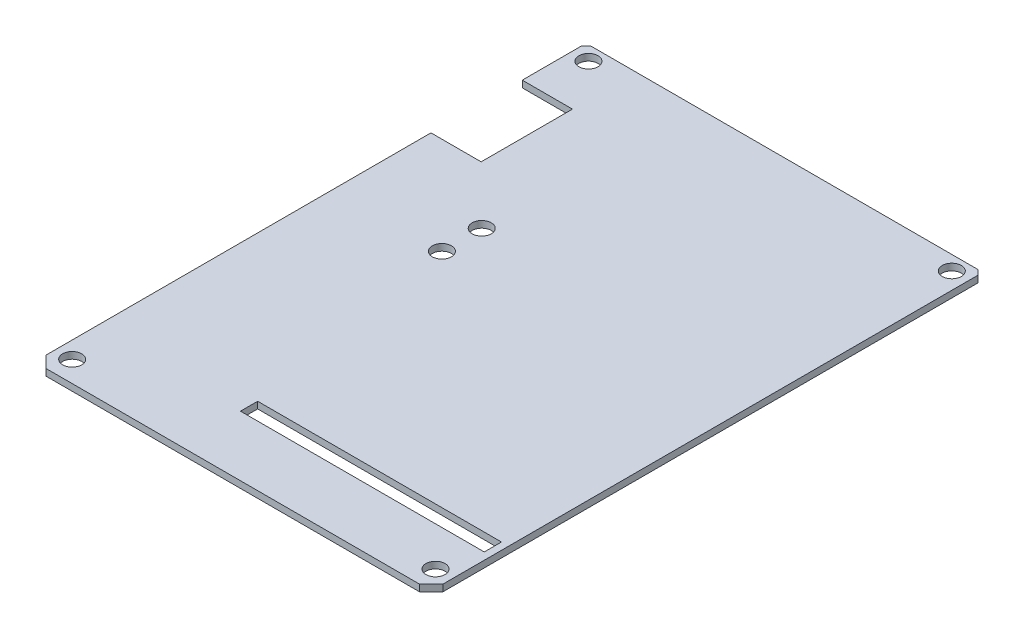
SolidWorks part; units mm, degrees
ref_plane "Front Plane" through (0, 0, 0) normal (0, 0, 1) x (1, 0, 0)
ref_plane "Top Plane" through (0, 0, 0) normal (0, 1, 0) x (1, 0, 0)
ref_plane "Right Plane" through (0, 0, 0) normal (1, 0, 0) x (0, 0, -1)
sketch "Sketch1" plane through (0, 0, 0) normal (0, 1, 0) x (1, 0, 0)
  line L17 (21.25, -27.4901) -> (19.2401, -29.5)
  line L33 (-21.25, 29.5) -> (21.25, 29.5)
  line L34 (-21.25, 29.5) -> (-21.25, -29.5)
  line L35 (-21.25, -29.5) -> (21.25, -29.5)
  line L36 (21.25, 29.5) -> (21.25, -29.5)
  line L37 (-21.25, 29.5) -> (21.25, -29.5) construction
  line L38 (-21.25, -29.5) -> (21.25, 29.5) construction
  line L39 (0, -29.5) -> (0, 29.5) construction
  line L40 (-21.25, -27.4901) -> (-19.2401, -29.5)
  line L41 (21.25, 0) -> (-21.25, 0) construction
  line L42 (21.25, 27.4901) -> (19.2401, 29.5)
  line L43 (-21.25, 27.4901) -> (-19.2401, 29.5)
  line L44 (-20.2401, 28.5) -> (20.2401, 28.5)
  line L45 (-20.2401, -28.5) -> (20.2401, -28.5)
  line L46 (-20.75, -27.9901) -> (-20.75, 27.9901)
  line L47 (20.75, 27.9901) -> (20.75, -27.9901)
  line L56 (-19, -27) -> (19, -27) construction
  circle A13 centre (-9.45, 6.2845) radius 1
  circle A18 centre (-19, -27) radius 1
  circle A19 centre (19, -27) radius 1
  circle A22 centre (-19, 27) radius 1
  circle A23 centre (19, 27) radius 1
  circle A24 centre (-9.45, 2.1155) radius 1
  point P4 (0, 0)
  point P12 (0, 0)
  point P14 (0, 0)
  point P21 (0, -27)
  point P22 (0, 0)
  point P24 (-12.6269, 17.0486)
  dimension "D1" = 42.5
  dimension "D6" = 2.0099
  dimension "D9" = 2
  dimension "D3" = 19
  dimension "D5" = 2.0099
  dimension "D2" = 59
  dimension "D12" = 1
  dimension "D4" = 2
  dimension "D8" = 27
  dimension "D13" = 0.5
  dimension "D14" = 0.5
extrude "Boss-Extrude1" add sketch "Sketch1" along normal blind 0.7 contours L34 L35 L17 L36 L33 A19 A13 region at (0.0253, 0, 0.0112)
sketch "Sketch2" plane through (0, 0.7, 0) normal (0, 1, 0) x (1, 0, 0)
  line L1 (-20, -22.9) -> (20, -22.9)
  line L2 (-20, -22.9) -> (-20, -21.1)
  line L3 (-20, -21.1) -> (20, -21.1)
  line L4 (20, -22.9) -> (20, -21.1)
  line L5 (-20, -22.9) -> (20, -21.1) construction
  line L6 (-20, -21.1) -> (20, -22.9) construction
  line L7 (0, 0) -> (0, -22.9) construction
  line L10 (-5.5029, -21.1) -> (-5.5029, -22.9)
  line L11 (-5.25, -22.6) -> (-5.25, -21.1) construction
  point P4 (0, -22)
  dimension "D1" = 22
  dimension "D2" = 20
  dimension "D3" = 1.8
  dimension "D4" = 0.2529
extrude "Cut-Extrude1" cut sketch "Sketch2" against normal blind 10 contours L3 L10 L1 L4 region at (7.2486, 0.7, 22)
sketch "Sketch5" plane through (0, 0.7, 0) normal (0, 1, 0) x (1, 0, 0)
  line L0 (-20.2401, -28.5) -> (20.2401, -28.5) construction
  line L1 (-19.5401, -28.5) -> (19.5401, -28.5) construction
  line L2 (-19.5401, -28.5) -> (-19.5401, -29.2) construction
  line L3 (-19.5401, -29.2) -> (19.5401, -29.2)
  line L4 (19.5401, -28.5) -> (19.5401, -29.2) construction
  line L5 (-19.5401, -28.5) -> (19.5401, -29.2) construction
  line L6 (-19.5401, -29.2) -> (19.5401, -28.5) construction
  line L7 (0, -28.5) -> (0, -32.1934) construction
  line L9 (-19.5401, -29.2) -> (-20.2401, -28.5)
  line L10 (19.5401, -29.2) -> (20.2401, -28.5)
  line L11 (-20.2401, -28.5) -> (20.2401, -28.5)
  line L12 (-20.75, -27.9901) -> (-20.2401, -28.5) construction
  point P4 (0, -28.85)
  point P11 (18.5758, -28.5)
  point P16 (-20.5591, -28.5)
  point P19 (0, 0)
  dimension "D1" = 0.7
extrude "Boss-Extrude2" add sketch "Sketch5" against normal up to surface (0.7 mm away) up to face at (19, 0, -26)
sketch "Sketch6" plane through (0, 0.7, 0) normal (0, 1, 0) x (1, 0, 0)
  line L0 (-20.75, -27.9901) -> (-20.75, 27.9901) construction
  line L1 (-20.75, 21.8236) -> (-15.5, 21.8236)
  line L2 (-20.75, 21.8236) -> (-20.75, 12.2736)
  line L3 (-20.75, 12.2736) -> (-15.5, 12.2736)
  line L4 (-15.5, 21.8236) -> (-15.5, 12.2736)
  line L5 (-20.75, 21.8236) -> (-15.5, 12.2736) construction
  line L6 (-20.75, 12.2736) -> (-15.5, 21.8236) construction
  line L7 (-12.75, 17.0486) -> (-25.5525, 17.0486) construction
  line L8 (-12.75, 21.4236) -> (-12.75, 12.6736) construction
  point P4 (-18.125, 17.0486)
  point P11 (0, 0)
  dimension "D1" = 9.55
  dimension "D2" = 5.25
extrude "Cut-Extrude2" cut sketch "Sketch6" against normal blind 6
